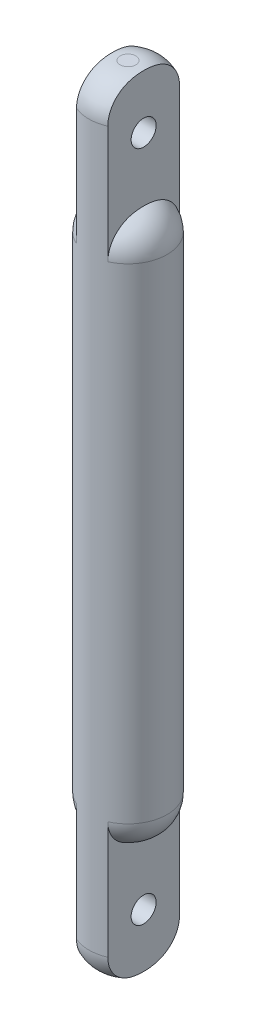
SolidWorks part; units mm, degrees
material "Alloy Steel (SS)"
ref_plane "Front Plane" through (0, 0, 0) normal (0, 0, 1) x (1, 0, 0)
ref_plane "Top Plane" through (0, 0, 0) normal (0, 1, 0) x (1, 0, 0)
ref_plane "Right Plane" through (0, 0, 0) normal (1, 0, 0) x (0, 0, -1)
sketch "Sketch10" plane through (0, 0, 0) normal (0, 1, 0) x (1, 0, 0)
  circle A0 centre (0, 0) radius 5
  dimension "D1" = 10
extrude "Boss-Extrude1" add sketch "Sketch10" along normal blind 100
ref_plane "Plane4" through (2, 0, 0) normal (1, 0, 0) x (0, 0, -1)
sketch "Sketch11" plane through (2, 0, 0) normal (1, 0, 0) x (0, 0, -1)
  line L0 (5, 0) -> (5, 100) construction
  line L1 (-5, 0) -> (5, 0)
  line L2 (-5, 0) -> (-5, 15)
  line L3 (-5, 15) -> (5, 15)
  line L4 (5, 0) -> (5, 15)
  point P5 (0, 0)
  dimension "D1" = 15
extrude "Cut-Extrude1" cut sketch "Sketch11" along normal blind 100
mirror "Mirror1" about plane through (0, 0, 0) normal (1, 0, 0) of "Cut-Extrude1"
sketch "Sketch12" plane through (-2, 0, 0) normal (-1, 0, 0) x (0, 0, 1)
  line L0 (4.5826, 0) -> (-4.5826, 0) construction
  circle A0 centre (0, 7) radius 1.6
  dimension "D1" = 3.2
  dimension "D2" = 7
extrude "Cut-Extrude2" cut sketch "Sketch12" against normal through all
ref_plane "Plane5" through (0, 50, 0) normal (0, -1, 0) x (-1, 0, 0)
mirror "Mirror7" about plane through (0, 50, 0) normal (0, -1, 0) of "Cut-Extrude1"
mirror "Mirror8" about plane through (0, 50, 0) normal (0, -1, 0) of "Mirror1"
mirror "Mirror9" about plane through (0, 50, 0) normal (0, -1, 0) of "Cut-Extrude2"
fillet "Fillet1" radius 4 4 edges at (-5, 15, 0) (5, 15, 0) (5, 85, 0) (-5, 85, 0)
fillet "Fillet2" radius 4 2 edges at (0, 0, 5) (0, 100, 5)
